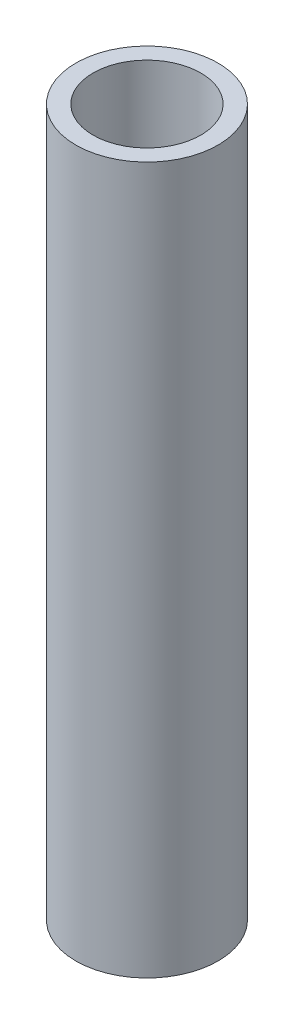
SolidWorks part; units mm, degrees
ref_plane "Front Plane" through (0, 0, 0) normal (0, 0, 1) x (1, 0, 0)
ref_plane "Top Plane" through (0, 0, 0) normal (0, 1, 0) x (1, 0, 0)
ref_plane "Right Plane" through (0, 0, 0) normal (1, 0, 0) x (0, 0, -1)
sketch "Sketch1" plane through (0, 0, 0) normal (0, 1, 0) x (1, 0, 0)
  circle A0 centre (0, 0) radius 0.825
  circle A1 centre (0, 0) radius 0.625
  dimension "D1" = 1.65
  dimension "D2" = 1.25
extrude "Boss-Extrude1" add sketch "Sketch1" along normal blind 8.2 contours A1 | A0
